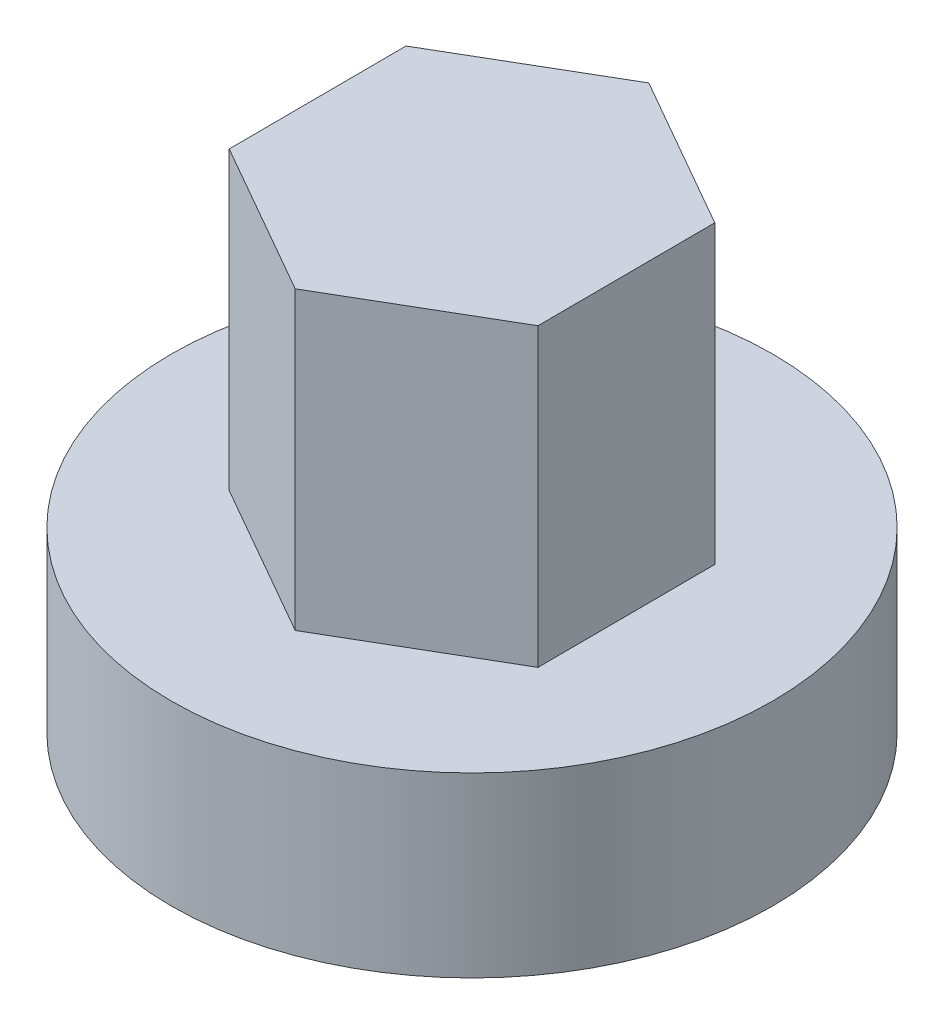
SolidWorks part; units mm, degrees
ref_plane "Front Plane" through (0, 0, 0) normal (0, 0, 1) x (1, 0, 0)
ref_plane "Top Plane" through (0, 0, 0) normal (0, 1, 0) x (1, 0, 0)
ref_plane "Right Plane" through (0, 0, 0) normal (1, 0, 0) x (0, 0, -1)
sketch "Sketch1" plane through (0, 0, 0) normal (0, 1, 0) x (1, 0, 0)
  line L1 (-0.0644, 14.9999) -> (-13.0224, 7.4442)
  line L2 (-13.0224, 7.4442) -> (-12.9581, -7.5557)
  line L3 (-12.9581, -7.5557) -> (0.0644, -14.9999)
  line L4 (0.0644, -14.9999) -> (13.0224, -7.4442)
  line L5 (13.0224, -7.4442) -> (12.9581, 7.5557)
  line L6 (12.9581, 7.5557) -> (-0.0644, 14.9999)
  circle A0 centre (0, 0) radius 25.4
  circle A1 centre (0, 0) radius 12.9904 construction
  dimension "D1" = 50.8
  dimension "D2" = 15
extrude "Boss-Extrude1" add sketch "Sketch1" against normal blind 15 contours L5 L6 L1 L2 L3 L4 | A0 L6 L5 L4 L3 L2 L1 region at (0, 0, 0) region at (-24.6816, 0, 0)
sketch "Sketch2" plane through (0, 0, 0) normal (0, 1, 0) x (1, 0, 0)
extrude "Boss-Extrude2" add sketch "Sketch1<3>" along normal blind 25 contours L5 L6 L1 L2 L3 L4 region at (0, 0, 0)
sketch "Sketch1<3>" plane through (0, 0, 0) normal (0, 1, 0) x (1, 0, 0) same geometry as "Sketch1"
